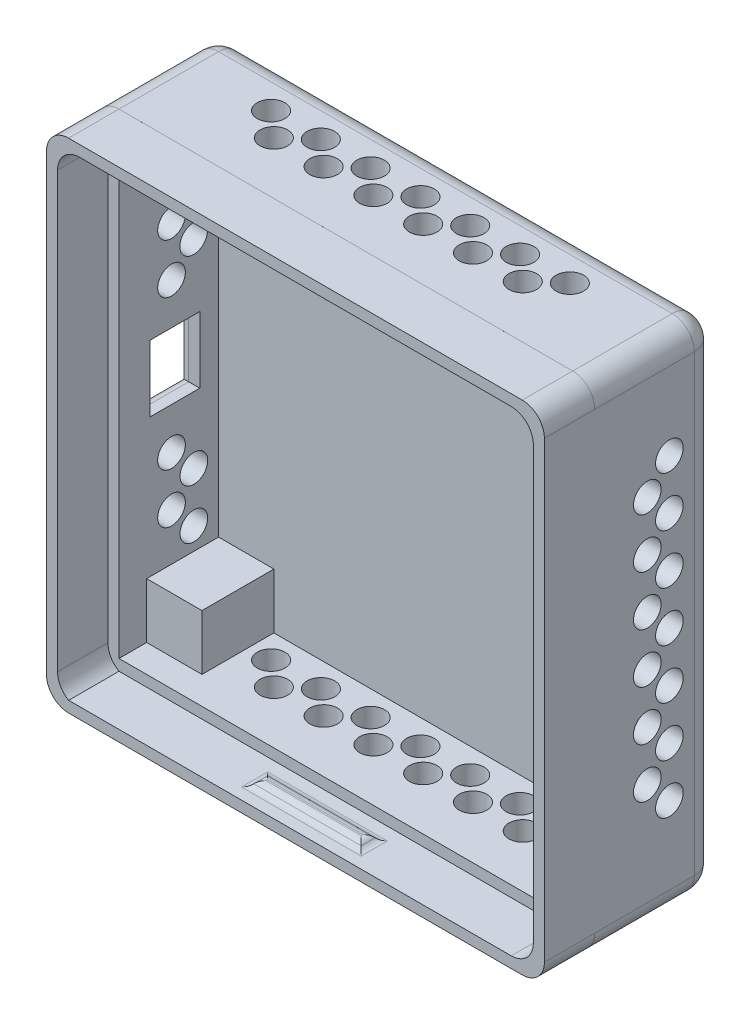
SolidWorks part; units mm, degrees
ref_plane "Piano frontale" through (0, 0, 0) normal (0, 0, 1) x (1, 0, 0)
ref_plane "Piano superiore" through (0, 0, 0) normal (0, 1, 0) x (1, 0, 0)
ref_plane "Piano destro" through (0, 0, 0) normal (1, 0, 0) x (0, 0, -1)
sketch "Schizzo2" plane through (0, 0, 0) normal (0, 0, 1) x (1, 0, 0)
  line L1 (0, 0) -> (45, 0)
  line L2 (0, 0) -> (0, 45)
  line L3 (0, 45) -> (45, 45)
  line L4 (45, 0) -> (45, 45)
  dimension "D1" = 45
  dimension "D2" = 45
extrude "Estrusione-Estrusione2" add sketch "Schizzo2" along normal blind 11
shell "Svuota1" thickness 2 removed face at (22.5, 22.5, 11)
fillet "Raccordo1" radius 2 4 edges at (45, 45, 5.5) (45, 0, 5.5) (0, 0, 5.5) (0, 45, 5.5)
fillet "Raccordo2" radius 2 8 edges at (44.4142, 0.5858, 0) (22.5, 0, 0) (0.5858, 0.5858, 0) (0, 22.5, 0) (0.5858, 44.4142, 0) (22.5, 45, 0) (44.4142, 44.4142, 0) (45, 22.5, 0)
sketch "Schizzo3" plane through (0, 0, 2) normal (0, 0, 1) x (1, 0, 0)
  line L0 (43, 43) -> (2, 43) construction
  line L1 (2, 43) -> (7, 43)
  line L2 (2, 43) -> (2, 38)
  line L3 (2, 38) -> (7, 38)
  line L4 (7, 43) -> (7, 38)
  line L5 (43, 43) -> (2, 43) construction
  dimension "D1" = 5
  dimension "D2" = 5
extrude "Estrusione-Estrusione3" add sketch "Schizzo3" along normal blind 6.5
sketch "Schizzo4" plane through (0, 0, 2) normal (0, 0, 1) x (1, 0, 0)
  line L1 (43, 2) -> (38, 2)
  line L2 (43, 2) -> (43, 7)
  line L3 (43, 7) -> (38, 7)
  line L4 (38, 2) -> (38, 7)
  dimension "D1" = 5
  dimension "D2" = 5
extrude "Estrusione-Estrusione4" add sketch "Schizzo4" along normal blind 6.5
fillet "Raccordo3" radius 4 2 edges at (38, 7, 5.25) (7, 38, 5.25)
sketch "Schizzo5" plane through (0, 0, 2) normal (0, 0, 1) x (1, 0, 0)
  line L0 (43, 2) -> (43, 43) construction
  line L1 (43, 43) -> (38, 43)
  line L2 (43, 43) -> (43, 38)
  line L3 (43, 38) -> (38, 38)
  line L4 (38, 43) -> (38, 38)
  line L5 (43, 43) -> (7, 43) construction
  line L7 (2, 2) -> (7, 2)
  line L8 (2, 2) -> (2, 7)
  line L9 (2, 7) -> (7, 7)
  line L10 (7, 2) -> (7, 7)
  dimension "D1" = 5
  dimension "D2" = 5
  dimension "D3" = 5
  dimension "D4" = 5
extrude "Estrusione-Estrusione5" add sketch "Schizzo5" along normal blind 6.5 contours L2 L1 L4 L3 | L8 L7 L10 L9
sketch "Schizzo12" plane through (0, 0, 11) normal (0, 0, 1) x (1, 0, 0)
  line L1 (0, 44.9999) -> (45, 44.9999)
  line L2 (0, 44.9999) -> (0, 43.9999)
  line L3 (0, 43.9999) -> (45, 43.9999)
  line L4 (45, 44.9999) -> (45, 43.9999)
  dimension "D1" = 45
  dimension "D2" = 1
extrude "Estrusione-Estrusione7" add sketch "Schizzo12" along normal blind 4.55
sketch "Schizzo13" plane through (0, 0, 11) normal (0, 0, 1) x (1, 0, 0)
  line L1 (45, 43.9999) -> (44, 43.9999)
  line L2 (45, 43.9999) -> (45, -0.0001)
  line L3 (45, -0.0001) -> (44, -0.0001)
  line L4 (44, 43.9999) -> (44, -0.0001)
  dimension "D1" = 44
  dimension "D2" = 1
extrude "Estrusione-Estrusione10" add sketch "Schizzo13" along normal blind 4.55
sketch "Schizzo15" plane through (0, 0, 11) normal (0, 0, 1) x (1, 0, 0)
  line L1 (44, -0.0001) -> (2, -0.0001)
  line L2 (44, -0.0001) -> (44, 0.9999)
  line L3 (44, 0.9999) -> (2, 0.9999)
  line L4 (2, -0.0001) -> (2, 0.9999)
  dimension "D1" = 1
  dimension "D2" = 42
extrude "Estrusione-Estrusione11" add sketch "Schizzo15" along normal blind 4.55
fillet "Raccordo4" radius 2 1 edges at (45, -0.0001, 13.275)
fillet "Raccordo5" radius 2 1 edges at (45, 44.9999, 13.275)
sketch "Schizzo17" plane through (0, 0, 11) normal (0, 0, 1) x (1, 0, 0)
  line L1 (0, 43.9999) -> (1, 43.9999)
  line L2 (0, 43.9999) -> (0, -0.0001)
  line L3 (0, -0.0001) -> (1, -0.0001)
  line L4 (1, 43.9999) -> (1, -0.0001)
  dimension "D1" = 1
  dimension "D2" = 44
extrude "Estrusione-Estrusione13" add sketch "Schizzo17" along normal blind 4.55
fillet "Raccordo6" radius 2 1 edges at (0, 44.9999, 13.275)
fillet "Raccordo7" radius 2 1 edges at (44, 0.9999, 13.275)
fillet "Raccordo8" radius 2 1 edges at (44, 43.9999, 13.275)
fillet "Raccordo9" radius 2 1 edges at (1, 43.9999, 13.275)
sketch "Schizzo18" plane through (0, 0, 11) normal (0, 0, 1) x (1, 0, 0)
  line L0 (1, -0.0001) -> (1, 41.9999) construction
  line L1 (2, -0.0001) -> (1, -0.0001)
  line L2 (2, -0.0001) -> (2, 0.9995)
  line L3 (2, 0.9995) -> (1, 0.9995)
  line L4 (1, -0.0001) -> (1, 0.9995)
extrude "Estrusione-Estrusione14" add sketch "Schizzo18" along normal blind 4.55
fillet "Raccordo10" radius 2 1 edges at (0, -0.0001, 13.275)
fillet "Raccordo11" radius 2 1 edges at (1, 0.9995, 13.275)
sketch "Schizzo22" plane through (0, 0.9999, 0) normal (0, 1, 0) x (1, 0, 0)
  line L5 (17.0049, -12.5647) -> (27.0049, -12.5647)
  line L6 (17.0049, -12.5647) -> (17.0049, -14.1147)
  line L7 (17.0049, -14.1147) -> (27.0049, -14.1147)
  line L8 (27.0049, -12.5647) -> (27.0049, -14.1147)
  dimension "D1" = 1.55
  dimension "D2" = 10
extrude "Estrusione-Estrusione15" add sketch "Schizzo22" along normal blind 0.5
fillet "Raccordo17" radius 0.74 4 edges at (27.0049, 1.4999, 13.3397) (22.0049, 1.4999, 14.1147) (17.0049, 1.4999, 13.3397) (22.0049, 1.4999, 12.5647)
fillet "Raccordo18" radius 0.74 4 edges at (22.0049, 0.9999, 12.5647) (27.0049, 0.9999, 13.3397) (17.0049, 0.9999, 13.3397) (22.0049, 0.9999, 14.1147)
sketch "Schizzo30" plane through (0, 43.9999, 0) normal (0, -1, 0) x (1, 0, 0)
  line L1 (17.0049, 14.1147) -> (27.0049, 14.1147)
  line L2 (17.0049, 14.1147) -> (17.0049, 12.5647)
  line L3 (17.0049, 12.5647) -> (27.0049, 12.5647)
  line L4 (27.0049, 14.1147) -> (27.0049, 12.5647)
extrude "Estrusione-Estrusione20" add sketch "Schizzo30" along normal blind 0.5 draft 1
fillet "Raccordo19" radius 0.74 4 edges at (22.0049, 43.4999, 12.5735) (26.9962, 43.4999, 13.3397) (22.0049, 43.4999, 14.106) (17.0136, 43.4999, 13.3397)
fillet "Raccordo20" radius 0.74 4 edges at (17.0049, 43.9999, 13.3397) (22.0049, 43.9999, 12.5647) (27.0049, 43.9999, 13.3397) (22.0049, 43.9999, 14.1147)
sketch "Schizzo34" plane through (43, 0, 0) normal (-1, 0, 0) x (0, 0, 1)
  circle A0 centre (4.2516, 35.9994) radius 1.25
  circle A1 centre (4.2516, 31.5034) radius 1.25
  circle A2 centre (4.2516, 27.0032) radius 1.25
  circle A3 centre (4.2516, 22.5053) radius 1.25
  circle A4 centre (4.2516, 18.0015) radius 1.25
  circle A5 centre (4.2516, 13.5036) radius 1.25
  circle A6 centre (4.2516, 9.0038) radius 1.25
  dimension "D1" = 2.5
  dimension "D2" = 2.5
  dimension "D3" = 2.5
  dimension "D4" = 2.5
  dimension "D5" = 2.5
  dimension "D6" = 2.5
  dimension "D7" = 2.5
extrude "Taglio-Estrusione7" cut sketch "Schizzo34" against normal blind 2
sketch "Schizzo35" plane through (43, 0, 0) normal (-1, 0, 0) x (0, 0, 1)
  circle A0 centre (6.2524, 33.7503) radius 1.25
  circle A1 centre (6.2524, 29.2487) radius 1.25
  circle A2 centre (6.2524, 24.7505) radius 1.25
  circle A3 centre (6.2524, 20.2517) radius 1.25
  circle A4 centre (6.2524, 15.7547) radius 1.25
  circle A5 centre (6.2524, 11.252) radius 1.25
  dimension "D1" = 2.5
  dimension "D2" = 2.5
  dimension "D3" = 2.5
  dimension "D4" = 2.5
  dimension "D5" = 2.5
  dimension "D6" = 2.5
extrude "Taglio-Estrusione8" cut sketch "Schizzo35" against normal blind 2
sketch "Schizzo36" plane through (0, 2, 0) normal (0, 1, 0) x (1, 0, 0)
  circle A0 centre (35.9868, -4.2536) radius 1.25
  circle A1 centre (31.4911, -4.2536) radius 1.25
  circle A2 centre (26.996, -4.2536) radius 1.25
  circle A3 centre (22.4971, -4.2536) radius 1.25
  circle A4 centre (17.9983, -4.2536) radius 1.25
  circle A5 centre (13.4999, -4.2536) radius 1.25
  circle A6 centre (9.0039, -4.2536) radius 1.25
  dimension "D1" = 2.5
  dimension "D2" = 2.5
  dimension "D3" = 2.5
  dimension "D4" = 2.5
  dimension "D5" = 2.5
  dimension "D6" = 2.5
  dimension "D7" = 2.5
extrude "Taglio-Estrusione9" cut sketch "Schizzo36" against normal blind 2
sketch "Schizzo37" plane through (0, 2, 0) normal (0, 1, 0) x (1, 0, 0)
  circle A0 centre (33.7463, -6.2534) radius 1.25
  circle A1 centre (29.2472, -6.2534) radius 1.25
  circle A2 centre (24.7485, -6.2534) radius 1.25
  circle A3 centre (20.2458, -6.2534) radius 1.25
  circle A4 centre (15.749, -6.2534) radius 1.25
  circle A5 centre (11.2492, -6.2534) radius 1.25
  dimension "D1" = 2.5
  dimension "D2" = 2.5
  dimension "D3" = 2.5
  dimension "D4" = 2.5
  dimension "D5" = 2.5
  dimension "D6" = 2.5
extrude "Taglio-Estrusione10" cut sketch "Schizzo37" against normal blind 2
sketch "Schizzo38" plane through (0, 43, 0) normal (0, -1, 0) x (-1, 0, 0)
  circle A0 centre (-8.9935, -4.2481) radius 1.25
  circle A1 centre (-13.4899, -4.2481) radius 1.25
  circle A2 centre (-17.9905, -4.2481) radius 1.25
  circle A3 centre (-22.4934, -4.2481) radius 1.25
  circle A4 centre (-26.9933, -4.2481) radius 1.25
  circle A5 centre (-31.495, -4.2481) radius 1.25
  circle A6 centre (-35.9965, -4.2481) radius 1.25
  dimension "D1" = 2.5
  dimension "D2" = 2.5
  dimension "D3" = 2.5
  dimension "D4" = 2.5
  dimension "D5" = 2.5
  dimension "D6" = 2.5
  dimension "D7" = 2.5
extrude "Taglio-Estrusione11" cut sketch "Schizzo38" against normal blind 2
sketch "Schizzo39" plane through (0, 43, 0) normal (0, -1, 0) x (-1, 0, 0)
  circle A0 centre (-11.2508, -6.2534) radius 1.25
  circle A1 centre (-15.7484, -6.2534) radius 1.25
  circle A2 centre (-20.2458, -6.2534) radius 1.25
  circle A3 centre (-24.7485, -6.2534) radius 1.25
  circle A4 centre (-29.2472, -6.2534) radius 1.25
  circle A5 centre (-33.7463, -6.2534) radius 1.25
  dimension "D1" = 2.5
  dimension "D2" = 2.5
  dimension "D3" = 2.5
  dimension "D4" = 2.5
  dimension "D5" = 2.5
  dimension "D6" = 2.5
extrude "Taglio-Estrusione12" cut sketch "Schizzo39" against normal blind 2
sketch "Schizzo40" plane through (2, 0, 0) normal (1, 0, 0) x (0, 0, -1)
  circle A0 centre (-4.2347, 8.9988) radius 1.25
  circle A1 centre (-4.2347, 13.4961) radius 1.25
  circle A2 centre (-4.2527, 35.9982) radius 1.25
  circle A3 centre (-4.2527, 31.4945) radius 1.25
  dimension "D1" = 2.5
  dimension "D2" = 2.5
  dimension "D5" = 2.5
  dimension "D6" = 2.5
sketch "Schizzo42" plane through (2, 0, 0) normal (1, 0, 0) x (0, 0, -1)
  line L0 (-8.2, 25.5052) -> (-3.7, 25.5052)
  line L5 (-8.2, 25.5052) -> (-8.2, 19.5052)
  line L6 (-8.2, 19.5052) -> (-3.7, 19.5052)
  line L7 (-3.7, 25.5052) -> (-3.7, 19.5052)
  dimension "D1" = 6
  dimension "D2" = 4.5
extrude "Taglio-Estrusione13" cut sketch "Schizzo42" against normal blind 2
fillet "Raccordo21" radius 1 4 edges at (0, 19.5052, 5.95) (0, 22.5052, 3.7) (0, 25.5052, 5.95) (0, 22.5052, 8.2)
extrude "Taglio-Estrusione14" cut sketch "Schizzo40" against normal blind 2
sketch "Schizzo43" plane through (2, 0, 0) normal (1, 0, 0) x (0, 0, -1)
  circle A0 centre (-6.2524, 11.2507) radius 1.25
  circle A1 centre (-6.2524, 15.7515) radius 1.25
  circle A2 centre (-6.2524, 29.2485) radius 1.25
  circle A3 centre (-6.2524, 33.7503) radius 1.25
  dimension "D1" = 2.5
  dimension "D2" = 2.5
  dimension "D3" = 2.5
  dimension "D4" = 2.5
extrude "Taglio-Estrusione15" cut sketch "Schizzo43" against normal blind 2
sketch "Schizzo44" plane through (0, 0, 0) normal (-1, 0, 0) x (0, 0, 1)
  line L1 (10.7483, 26.35) -> (13.3283, 26.35)
  line L2 (10.7483, 26.35) -> (10.7483, 25.75)
  line L3 (10.7483, 25.75) -> (13.3283, 25.75)
  line L4 (13.3283, 26.35) -> (13.3283, 25.75)
  point P4 (0, 0)
  dimension "D1" = 0.6
  dimension "D2" = 2.58
extrude "Estrusione-Estrusione21" add sketch "Schizzo44" along normal blind 0.7
sketch "Schizzo45" plane through (0, 0, 0) normal (-1, 0, 0) x (0, 0, 1)
  circle A0 centre (12.036, 19.7623) radius 1.29
  circle A1 centre (12.036, 19.7623) radius 1
  dimension "D1" = 2.58
  dimension "D2" = 2
extrude "Estrusione-Estrusione22" add sketch "Schizzo45" along normal blind 0.7
fillet "Raccordo23" radius 0.1 6 edges at (-0.7, 26.05, 13.3283) (-0.7, 25.75, 12.0383) (-0.7, 26.05, 10.7483) (-0.7, 26.35, 12.0383) (-0.7, 19.7623, 13.326) (-0.7, 19.7623, 13.036)
sketch "Schizzo47" plane through (0, 0, 0) normal (0, 0, -1) x (-1, 0, 0)
